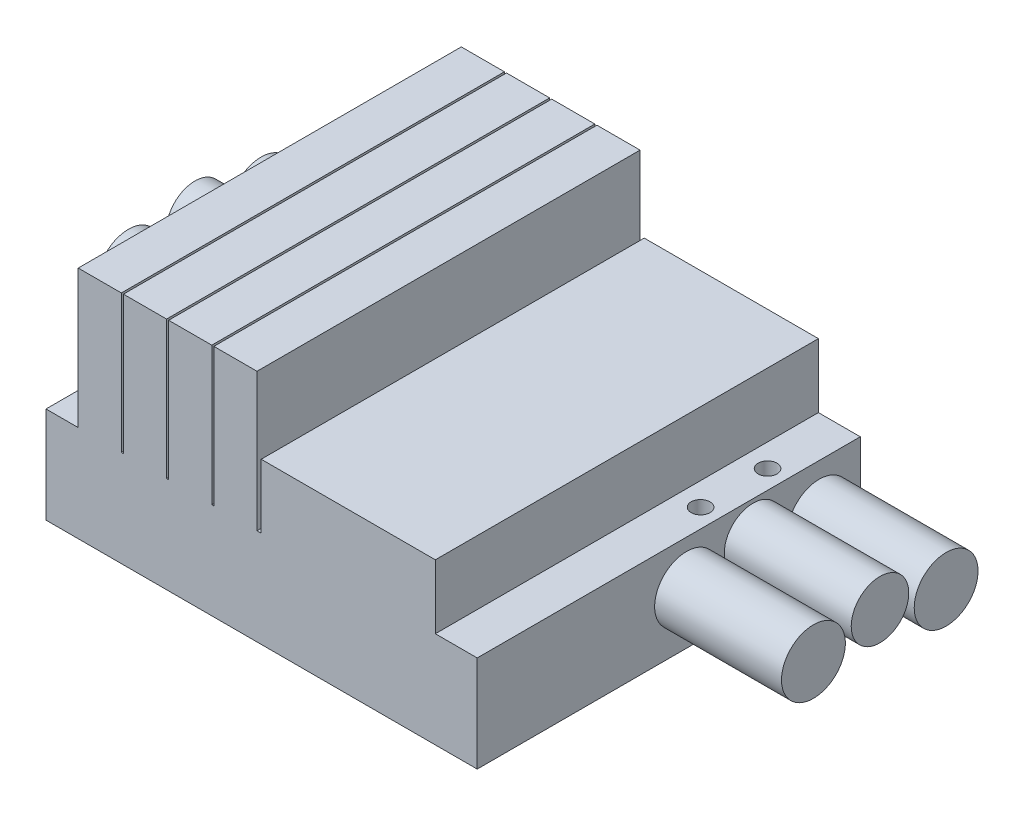
SolidWorks part; units mm, degrees
ref_plane "Front Plane" through (0, 0, 0) normal (0, 0, 1) x (1, 0, 0)
ref_plane "Top Plane" through (0, 0, 0) normal (0, 1, 0) x (1, 0, 0)
ref_plane "Right Plane" through (0, 0, 0) normal (1, 0, 0) x (0, 0, -1)
sketch "Sketch1" plane through (0, 0, 0) normal (0, 1, 0) x (1, 0, 0)
  line L0 (-47, 45.75) -> (-47, 30.25) construction
  line L1 (-51.5, -45.75) -> (51.5, -45.75)
  line L2 (-51.5, -45.75) -> (-51.5, 45.75)
  line L3 (-51.5, 45.75) -> (51.5, 45.75)
  line L4 (51.5, -45.75) -> (51.5, 45.75)
  line L5 (-51.5, -45.75) -> (51.5, 45.75) construction
  line L6 (-51.5, 45.75) -> (51.5, -45.75) construction
  line L7 (-47, 45.75) -> (-47, 14.25) construction
  line L8 (-47, 30.25) -> (-47, 28.1) construction
  line L9 (-47, 14.25) -> (-47, 12.1) construction
  line L10 (-47, 28.1) -> (-51.5, 28.1) construction
  line L11 (-47, 12.1) -> (-51.5, 12.1) construction
  line L12 (-47, 12.1) -> (47, 12.1) construction
  line L13 (-47, 28.1) -> (47, 28.1) construction
  circle A0 centre (-47, 28.1) radius 2.15
  circle A1 centre (-47, 12.1) radius 2.15
  circle A2 centre (47, 28.1) radius 2.25
  circle A3 centre (47, 12.1) radius 2.25
  point P0 (0, 0)
  dimension "D9" = 4.5
  dimension "D10" = 4.5
  dimension "D1" = 91.5
  dimension "D2" = 103
  dimension "D3" = 15.5
  dimension "D4" = 31.5
  dimension "D5" = 2.15
  dimension "D6" = 2.15
  dimension "D7" = 4.5
  dimension "D8" = 4.5
  dimension "D11" = 94
  dimension "D12" = 94
extrude "Boss-Extrude1" add sketch "Sketch1" along normal blind 23 contours A3 | A2 | L2 L1 L4 L3 | A0 | A1
sketch "Sketch2" plane through (-51.5, 0, 0) normal (-1, 0, 0) x (0, 0, 1)
  line L0 (-45.75, 11.5) -> (-35.95, 11.5) construction
  line L1 (-45.75, 15.2) -> (-20.15, 15.2) construction
  line L2 (-35.95, 11.5) -> (-35.95, 0) construction
  line L4 (-45.75, 23) -> (-45.75, 0) construction
  line L5 (-20.15, 15.2) -> (-20.15, 0) construction
  line L6 (-45.75, 12.4) -> (-4.25, 12.4) construction
  line L7 (-4.25, 12.4) -> (-4.25, 0) construction
  circle A0 centre (-35.95, 11.5) radius 7.625
  circle A1 centre (-20.15, 15.2) radius 6.875
  circle A2 centre (-4.25, 12.4) radius 7.625
  dimension "D3" = 15.25
  dimension "D6" = 13.75
  dimension "D9" = 15.25
  dimension "D1" = 9.8
  dimension "D2" = 11.5
  dimension "D4" = 25.6
  dimension "D5" = 15.2
  dimension "D7" = 12.4
  dimension "D8" = 41.5
extrude "Boss-Extrude2" add sketch "Sketch2" along normal blind 30.31 from surface contours A1 | A0 | A2 starting at face at (-51.5, 11.5, 0)
sketch "Sketch4" plane through (0, 0, -45.75) normal (0, 0, -1) x (-1, 0, 0)
  line L0 (-51.5, 5.4) -> (5.8, 5.4) construction
  line L1 (-51.5, 19.125) -> (-51.5, 3.875) construction
  line L2 (5.8, 5.4) -> (5.8, 23) construction
  line L4 (-51.5, 17.6) -> (0.8, 17.6) construction
  line L5 (-51.5, 23) -> (-51.5, 0) construction
  line L6 (0.8, 17.6) -> (0.8, 23) construction
  circle A0 centre (5.8, 5.4) radius 4.9
  circle A1 centre (0.8, 17.6) radius 4.9
  circle A2 centre (11.3, 17.6) radius 4.9
  circle A3 centre (16.3, 5.4) radius 4.9
  circle A4 centre (21.8, 17.6) radius 4.9
  circle A5 centre (26.8, 5.4) radius 4.9
  circle A6 centre (32.3, 17.6) radius 4.9
  circle A7 centre (37.3, 5.4) radius 4.9
  dimension "D5" = 9.8
  dimension "D6" = 9.8
  dimension "D1" = 57.3
  dimension "D2" = 17.6
  dimension "D3" = 52.3
  dimension "D4" = 5.4
  dimension "D7" = 4
extrude "Boss-Extrude3" add sketch "Sketch4" along normal blind 14.15
extrude "Boss-Extrude4" add sketch "Sketch2<7>" against normal blind 30.31 from surface starting at face at (51.5, 11.5, 0)
sketch "Sketch2<7>" plane through (-51.5, 0, 0) normal (-1, 0, 0) x (0, 0, 1) same geometry as "Sketch2"
sketch "Sketch6" plane through (0, 23, 0) normal (0, 1, 0) x (1, 0, 0)
  line L0 (51.5, 41.6244) -> (41.5, 41.6244) construction
  line L1 (51.5, -45.75) -> (51.5, 45.75) construction
  line L2 (51.5, 0) -> (-51.5, 0) construction
  line L3 (-51.5, -45.75) -> (-51.5, 45.75) construction
  line L9 (41.5, 41.6244) -> (41.5, -45.75) construction
  line L10 (-51.5, -45.75) -> (51.5, -45.75) construction
  line L11 (-51.5, 45.75) -> (51.5, 45.75) construction
  line L12 (41.5, -45.75) -> (-0.1, -45.75)
  line L13 (41.5, -45.75) -> (41.5, 45.75)
  line L14 (41.5, 45.75) -> (-0.1, 45.75)
  line L15 (-0.1, -45.75) -> (-0.1, 45.75)
  line L16 (-0.1, 9.576) -> (-1.1, 9.576) construction
  line L17 (-1.1, 9.576) -> (-1.1, 45.75) construction
  line L18 (-11.9, 45.75) -> (-11.9, -45.75)
  line L19 (-1.1, 45.75) -> (-11.4, 45.75)
  line L20 (-1.1, 45.75) -> (-1.1, -45.75)
  line L21 (-1.1, -45.75) -> (-11.4, -45.75)
  line L22 (-11.4, 45.75) -> (-11.4, -45.75)
  line L23 (-11.9, 45.75) -> (-22.2, 45.75)
  line L24 (-22.2, 45.75) -> (-22.2, -45.75)
  line L25 (-11.9, -45.75) -> (-22.2, -45.75)
  line L26 (-22.7, 45.75) -> (-22.7, -45.75)
  line L27 (-22.7, 45.75) -> (-33, 45.75)
  line L28 (-33, 45.75) -> (-33, -45.75)
  line L29 (-22.7, -45.75) -> (-33, -45.75)
  line L30 (-33.5, 45.75) -> (-33.5, -45.75)
  line L31 (-33.5, 45.75) -> (-43.8, 45.75)
  line L32 (-43.8, 45.75) -> (-43.8, -45.75)
  line L33 (-33.5, -45.75) -> (-43.8, -45.75)
  dimension "D1" = 10
  dimension "D2" = 41.6
  dimension "D3" = 1
  dimension "D4" = 10.3
  dimension "D5" = 4
extrude "Boss-Extrude5" add sketch "Sketch6" along normal blind 15.3 contours L13 L12 L15 L14
extrude "Boss-Extrude7" add sketch "Sketch6<5>" along normal blind 33 contours L20 L21 L22 L19 | L18 L25 L24 L23 | L26 L29 L28 L27 | L30 L33 L32 L31
sketch "Sketch6<5>" plane through (0, 23, 0) normal (0, 1, 0) x (1, 0, 0) same geometry as "Sketch6"
